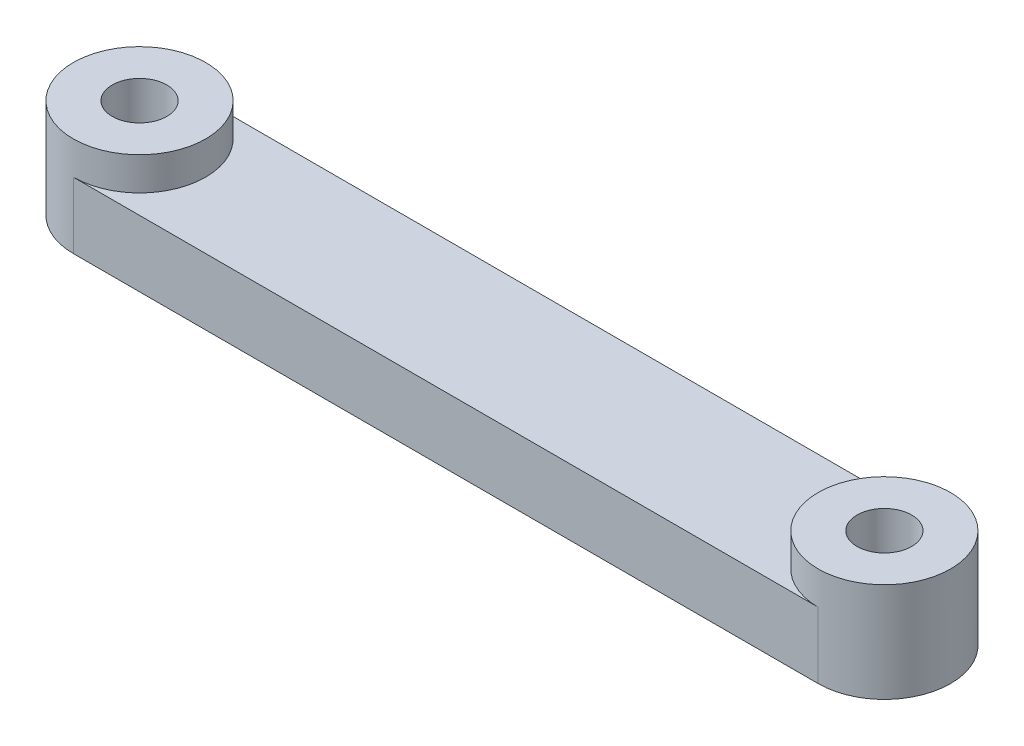
SolidWorks part; units mm, degrees
ref_plane "Front Plane" through (0, 0, 0) normal (0, 0, 1) x (1, 0, 0)
ref_plane "Top Plane" through (0, 0, 0) normal (0, 1, 0) x (1, 0, 0)
ref_plane "Right Plane" through (0, 0, 0) normal (1, 0, 0) x (0, 0, -1)
sketch "Sketch1" plane through (0, 0, 0) normal (0, 1, 0) x (1, 0, 0)
  line L0 (-22.5, 0) -> (22.5, 0) construction
  line L2 (-22.5, 4) -> (22.5, 4)
  line L3 (-22.5, -4) -> (22.5, -4)
  arc A0 (-22.5, 4) -> (-22.5, -4) centre (-22.5, 0) ccw
  arc A1 (22.5, -4) -> (22.5, 4) centre (22.5, 0) ccw
  circle A2 centre (-22.5, 0) radius 1.65
  circle A3 centre (22.5, 0) radius 1.65
  point P5 (0, 0)
  dimension "D1" = 4
  dimension "D2" = 45
  dimension "D3" = 3.3
  dimension "D4" = 3.3
extrude "Boss-Extrude1" add sketch "Sketch1" along normal blind 4
sketch "Sketch2" plane through (0, 4, 0) normal (0, 1, 0) x (1, 0, 0)
  circle A0 centre (-22.5, 0) radius 4
  circle A1 centre (-22.5, 0) radius 1.65
  circle A2 centre (22.5, 0) radius 1.65
  circle A3 centre (22.5, 0) radius 4
extrude "Boss-Extrude2" add sketch "Sketch2" along normal blind 2
